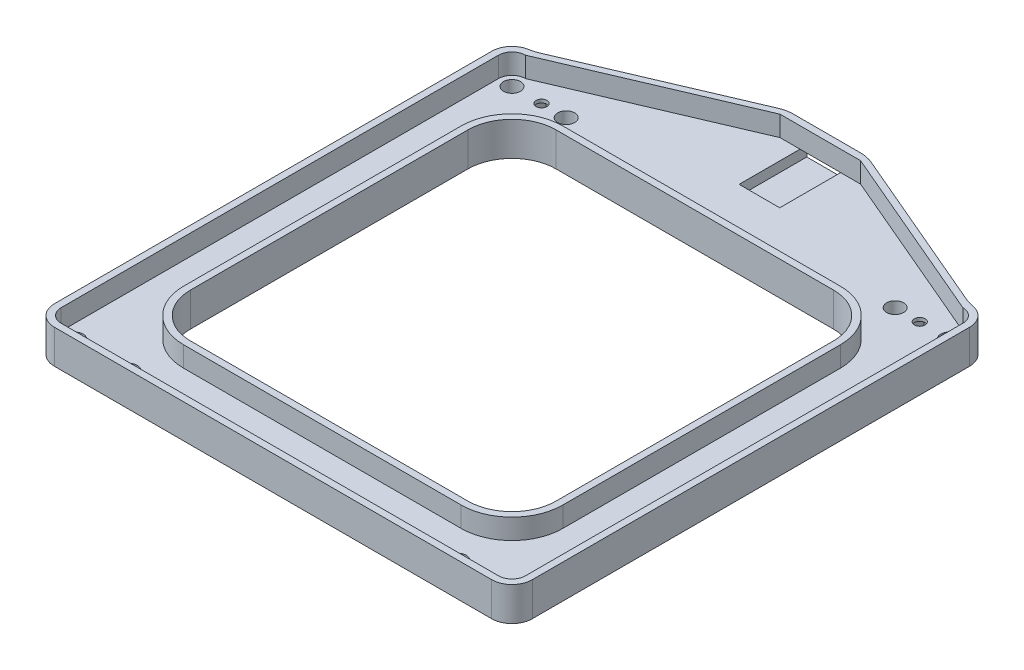
SolidWorks part; units mm, degrees
ref_plane "Front Plane" through (0, 0, 0) normal (0, 0, 1) x (1, 0, 0)
ref_plane "Top Plane" through (0, 0, 0) normal (0, 1, 0) x (1, 0, 0)
ref_plane "Right Plane" through (0, 0, 0) normal (1, 0, 0) x (0, 0, -1)
sketch "Sketch1" plane through (0, 0, 0) normal (0, 1, 0) x (1, 0, 0)
  line L0 (-64.6, 70.6) -> (-13.7811, 92.2969)
  line L5 (-64.6, -70.6) -> (64.6, -70.6)
  line L6 (-70.6, -64.6) -> (-70.6, 64.6)
  line L7 (-64.6, 70.6) -> (64.6, 70.6) construction
  line L8 (70.6, -64.6) -> (70.6, 64.6)
  line L9 (-70.6, -70.6) -> (70.6, 70.6) construction
  line L10 (-70.6, 70.6) -> (70.6, -70.6) construction
  line L11 (-41, -54) -> (41, -54)
  line L12 (-54, -41) -> (-54, 41)
  line L13 (-41, 54) -> (41, 54)
  line L14 (54, -41) -> (54, 41)
  line L15 (-54, -54) -> (54, 54) construction
  line L16 (-54, 54) -> (54, -54) construction
  line L17 (-9.8546, 93.1) -> (9.8546, 93.1)
  line L18 (13.7811, 92.2969) -> (64.6, 70.6)
  arc A0 (-70.6, -64.6) -> (-64.6, -70.6) centre (-64.6, -64.6) ccw
  arc A1 (64.6, -70.6) -> (70.6, -64.6) centre (64.6, -64.6) ccw
  arc A2 (70.6, 64.6) -> (64.6, 70.6) centre (64.6, 64.6) ccw
  arc A3 (-64.6, 70.6) -> (-70.6, 64.6) centre (-64.6, 64.6) ccw
  arc A4 (-54, -41) -> (-41, -54) centre (-41, -41) ccw
  arc A5 (41, -54) -> (54, -41) centre (41, -41) ccw
  arc A6 (54, 41) -> (41, 54) centre (41, 41) ccw
  arc A7 (-41, 54) -> (-54, 41) centre (-41, 41) ccw
  arc A8 (13.7811, 92.2969) -> (9.8546, 93.1) centre (9.8546, 83.1) ccw
  arc A9 (-9.8546, 93.1) -> (-13.7811, 92.2969) centre (-9.8546, 83.1) ccw
  point P0 (0, 0)
  point P18 (0, 0)
  point P39 (11.9, 93.1)
  point P42 (-11.9, 93.1)
  dimension "D3" = 6
  dimension "D6" = 13
  dimension "D9" = 10
  dimension "D1" = 141.2
  dimension "D2" = 141.2
  dimension "D4" = 108
  dimension "D5" = 108
  dimension "D7" = 22.5
  dimension "D8" = 23.8
extrude "Boss-Extrude1" add sketch "Sketch1" along normal blind 10
sketch "Sketch2" plane through (0, 10, 0) normal (0, 1, 0) x (1, 0, 0)
  line L0 (-64.6, 68.6) -> (-11.9, 91.1)
  line L1 (-64.6, -68.6) -> (64.6, -68.6)
  line L2 (-68.6, -64.6) -> (-68.6, 64.6)
  line L3 (-64.6, 68.6) -> (64.6, 68.6) construction
  line L4 (68.6, -64.6) -> (68.6, 64.6)
  line L5 (-68.6, -68.6) -> (68.6, 68.6) construction
  line L6 (-68.6, 68.6) -> (68.6, -68.6) construction
  line L7 (-41, -56) -> (41, -56)
  line L8 (-56, -41) -> (-56, 41)
  line L9 (-41, 56) -> (41, 56)
  line L10 (56, -41) -> (56, 41)
  line L11 (-56, -56) -> (56, 56) construction
  line L12 (-56, 56) -> (56, -56) construction
  line L13 (-11.9, 91.1) -> (11.9, 91.1)
  line L14 (11.9, 91.1) -> (64.6, 68.6)
  line L16 (-13.7811, 92.2969) -> (-64.6, 70.6) construction
  arc A0 (-68.6, -64.6) -> (-64.6, -68.6) centre (-64.6, -64.6) ccw
  arc A1 (64.6, -68.6) -> (68.6, -64.6) centre (64.6, -64.6) ccw
  arc A2 (68.6, 64.6) -> (64.6, 68.6) centre (64.6, 64.6) ccw
  arc A3 (-64.6, 68.6) -> (-68.6, 64.6) centre (-64.6, 64.6) ccw
  arc A4 (-56, -41) -> (-41, -56) centre (-41, -41) ccw
  arc A5 (41, -56) -> (56, -41) centre (41, -41) ccw
  arc A6 (56, 41) -> (41, 56) centre (41, 41) ccw
  arc A7 (-41, 56) -> (-56, 41) centre (-41, 41) ccw
  point P0 (0, 0)
  point P8 (0, 91.1)
  point P20 (0, 0)
  point P44 (0, 68.6)
  dimension "D3" = 4
  dimension "D6" = 15
  dimension "D1" = 2
  dimension "D2" = 2
  dimension "D4" = 2
  dimension "D5" = 2
  dimension "D7" = 2
extrude "Cut-Extrude1" cut sketch "Sketch2" against normal blind 6
sketch "Sketch3" plane through (0, 0, 0) normal (0, 1, 0) x (1, 0, 0)
  line L4 (0, -5.5) -> (0, 5.5) construction
  line L6 (-5.5, 0) -> (5.5, 0) construction
  circle A0 centre (-64.6, 64.6) radius 2.5
  circle A1 centre (-48.6, 64.6) radius 2.5
  circle A14 centre (-55.87, 64.6) radius 1.6
  circle A15 centre (55.87, 64.6) radius 1.6
  circle A16 centre (48.6, 64.6) radius 2.5
  circle A17 centre (64.6, 64.6) radius 2.5
  circle A18 centre (64.6, -64.6) radius 2.5
  circle A19 centre (48.6, -64.6) radius 2.5
  circle A20 centre (55.87, -64.6) radius 1.6
  circle A21 centre (-55.87, -64.6) radius 1.6
  circle A22 centre (-48.6, -64.6) radius 2.5
  circle A23 centre (-64.6, -64.6) radius 2.5
  dimension "D1" = 5
  dimension "D6" = 3.2
  dimension "D2" = 6
  dimension "D3" = 6
  dimension "D4" = 16
  dimension "D5" = 7.27
extrude "Cut-Extrude5" cut sketch "Sketch3" along normal through all
sketch "Sketch6" plane through (0, 0, 0) normal (0, -1, 0) x (1, 0, 0)
  line L0 (5.5, 0) -> (-5.5, 0) construction
  line L1 (-52.4059, 64.6) -> (-54.1379, 67.6)
  line L2 (-54.1379, 67.6) -> (-57.6021, 67.6)
  line L3 (-57.6021, 67.6) -> (-59.3341, 64.6)
  line L4 (-59.3341, 64.6) -> (-57.6021, 61.6)
  line L5 (-57.6021, 61.6) -> (-54.1379, 61.6)
  line L6 (-54.1379, 61.6) -> (-52.4059, 64.6)
  line L7 (-54.1379, -61.6) -> (-52.4059, -64.6)
  line L8 (-57.6021, -61.6) -> (-54.1379, -61.6)
  line L9 (-59.3341, -64.6) -> (-57.6021, -61.6)
  line L10 (-57.6021, -67.6) -> (-59.3341, -64.6)
  line L11 (-54.1379, -67.6) -> (-57.6021, -67.6)
  line L12 (-52.4059, -64.6) -> (-54.1379, -67.6)
  line L13 (0, -5.5) -> (0, 5.5) construction
  line L14 (52.4059, -64.6) -> (54.1379, -67.6)
  line L15 (54.1379, -67.6) -> (57.6021, -67.6)
  line L16 (57.6021, -67.6) -> (59.3341, -64.6)
  line L17 (59.3341, -64.6) -> (57.6021, -61.6)
  line L18 (57.6021, -61.6) -> (54.1379, -61.6)
  line L19 (54.1379, -61.6) -> (52.4059, -64.6)
  line L20 (54.1379, 61.6) -> (52.4059, 64.6)
  line L21 (57.6021, 61.6) -> (54.1379, 61.6)
  line L22 (59.3341, 64.6) -> (57.6021, 61.6)
  line L23 (57.6021, 67.6) -> (59.3341, 64.6)
  line L24 (54.1379, 67.6) -> (57.6021, 67.6)
  line L25 (52.4059, 64.6) -> (54.1379, 67.6)
  circle A0 centre (-55.87, 64.6) radius 3 construction
  circle A1 centre (-55.87, -64.6) radius 3 construction
  circle A2 centre (55.87, -64.6) radius 3 construction
  circle A3 centre (55.87, 64.6) radius 3 construction
  point P11 (-48.6, 64.6)
  point P22 (-48.6, -64.6)
  point P41 (48.6, -64.6)
  point P42 (48.6, 64.6)
  dimension "D1" = 6
extrude "Cut-Extrude6" cut sketch "Sketch6" against normal blind 3
fillet "Fillet1" radius 10 2 edges at (64.6, 5, -70.6) (-64.6, 5, -70.6)
sketch "Sketch7" plane through (0, 0, -93.1) normal (0, 0, -1) x (-1, 0, 0)
  line L0 (-11.9, 4) -> (11.9, 4) construction
  line L1 (-6, 1) -> (6, 1)
  line L2 (-6, 1) -> (-6, 4)
  line L3 (-6, 4) -> (6, 4)
  line L4 (6, 1) -> (6, 4)
  line L5 (-6, 1) -> (6, 4) construction
  line L6 (-6, 4) -> (6, 1) construction
  point P0 (0, 2.5)
  point P7 (0, 0)
  dimension "D1" = 12
  dimension "D2" = 3
extrude "Cut-Extrude7" cut sketch "Sketch7" against normal blind 20
